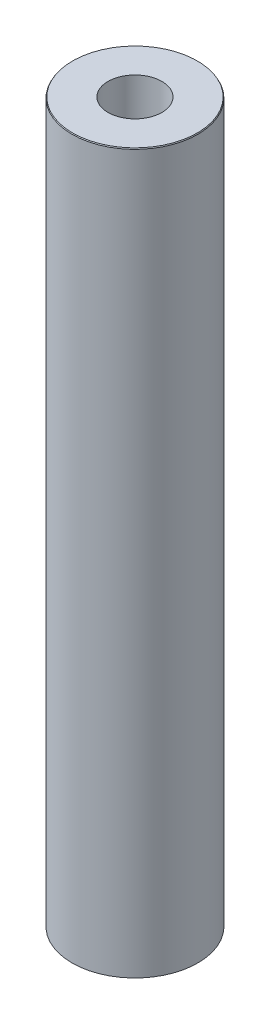
SolidWorks part; units mm, degrees
ref_plane "Front Plane" through (0, 0, 0) normal (0, 0, 1) x (1, 0, 0)
ref_plane "Top Plane" through (0, 0, 0) normal (0, 1, 0) x (1, 0, 0)
ref_plane "Right Plane" through (0, 0, 0) normal (1, 0, 0) x (0, 0, -1)
sketch "Sketch1" plane through (0, 0, 0) normal (0, 1, 0) x (1, 0, 0)
  circle A0 centre (0, 0) radius 52.5
  dimension "SHAFT_OD" = 105
extrude "Boss-Extrude1" add sketch "Sketch1" along normal blind 600
sketch "Sketch2" plane through (0, 0, 0) normal (0, 1, 0) x (1, 0, 0)
  circle A0 centre (0, 0) radius 22.4772
  dimension "BORE_D" = 44.9544
extrude "Cut-Extrude1" cut sketch "Sketch2" along normal through all
chamfer "Chamfer1" distance 0.7748 angle 30 2 edges at (0, 600, 52.5) (0, 0, 52.5) first distance on face at (0, 600, 52.5) first distance on face at (0, 0, 22.4772)
